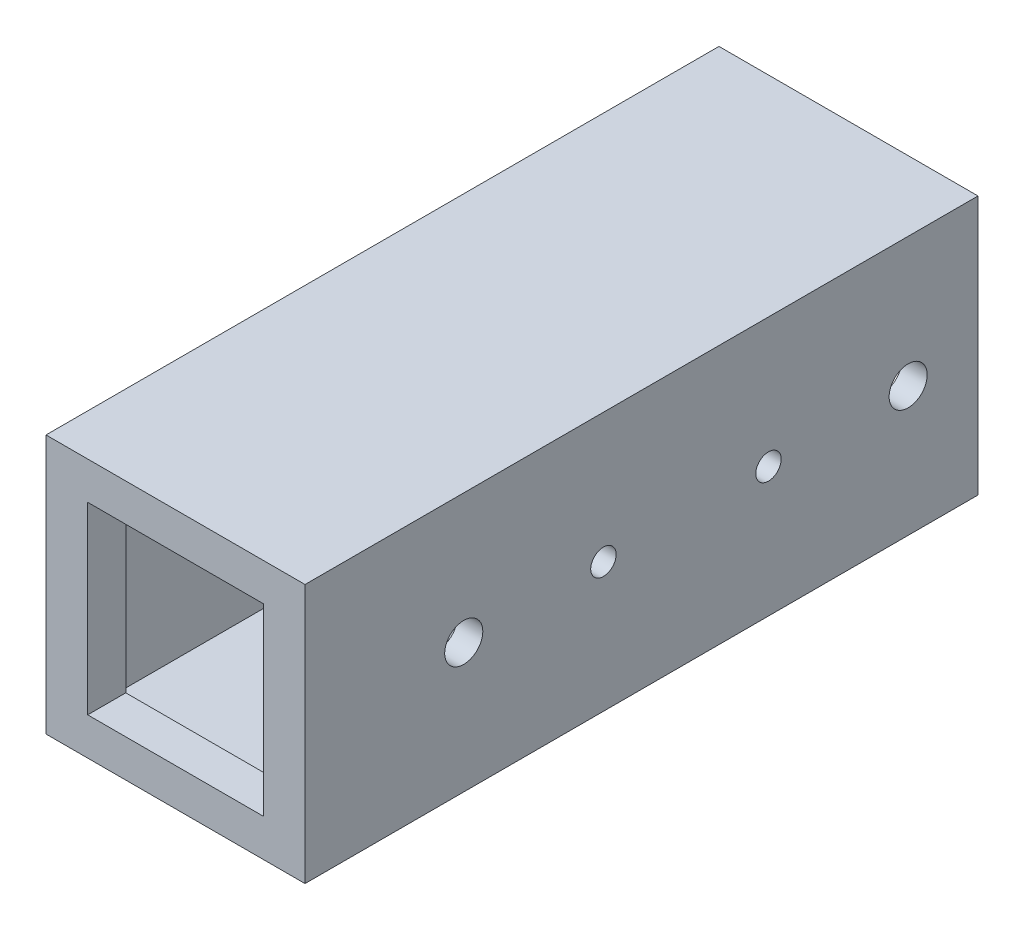
SolidWorks part; units mm, degrees
ref_plane "Front Plane" through (0, 0, 0) normal (0, 0, 1) x (1, 0, 0)
ref_plane "Top Plane" through (0, 0, 0) normal (0, 1, 0) x (1, 0, 0)
ref_plane "Right Plane" through (0, 0, 0) normal (1, 0, 0) x (0, 0, -1)
ref_axis "Axis1" through (0, 0, 0.5) along (0, 0, -1)
sketch "Sketch1" plane through (0, 0, 0) normal (0, 0, 1) x (1, 0, 0)
  line L5 (-10.2, -10.2) -> (10.2, -10.2)
  line L14 (-10.2, -10.2) -> (-10.2, 10.2)
  line L15 (-10.2, 10.2) -> (10.2, 10.2)
  line L16 (10.2, -10.2) -> (10.2, 10.2)
  line L17 (-10.2, -10.2) -> (10.2, 10.2) construction
  line L18 (-10.2, 10.2) -> (10.2, -10.2) construction
  line L19 (-8.2, -8.2) -> (8.2, -8.2)
  line L20 (-8.2, -8.2) -> (-8.2, 8.2)
  line L21 (-8.2, 8.2) -> (8.2, 8.2)
  line L22 (8.2, -8.2) -> (8.2, 8.2)
  line L23 (-8.2, -8.2) -> (8.2, 8.2) construction
  line L24 (-8.2, 8.2) -> (8.2, -8.2) construction
  point P0 (0, 0)
  point P6 (0, 0)
  dimension "D1" = 16.4
  dimension "D2" = 2
extrude "Boss-Extrude1" add sketch "Sketch1" against normal blind 50
sketch "Sketch2" plane through (0, 0, 0) normal (0, 0, 1) x (1, 0, 0)
  line L1 (10.2, 10.2) -> (-10.2, 10.2)
  line L2 (10.2, 10.2) -> (10.2, -10.2)
  line L3 (10.2, -10.2) -> (-10.2, -10.2)
  line L4 (-10.2, 10.2) -> (-10.2, -10.2)
  line L9 (6.9174, -7.2486) -> (-6.9174, -7.2486)
  line L10 (6.9174, -7.2486) -> (6.9174, 7.2486)
  line L11 (6.9174, 7.2486) -> (-6.9174, 7.2486)
  line L12 (-6.9174, -7.2486) -> (-6.9174, 7.2486)
  line L13 (6.9174, -7.2486) -> (-6.9174, 7.2486) construction
  line L14 (6.9174, 7.2486) -> (-6.9174, -7.2486) construction
  point P4 (0, 0)
  point P5 (0, 0)
extrude "Boss-Extrude2" add sketch "Sketch2" along normal blind 3
sketch "Sketch3" plane through (10.2, 0, 0) normal (1, 0, 0) x (0, 0, -1)
  circle A1 centre (44.5, 0) radius 2.1 construction
  circle A4 centre (20.5, 0) radius 1
  circle A5 centre (33.5, 0) radius 3 construction
  circle A6 centre (9.5, 0) radius 1.5
  circle A7 centre (20.5, 0) radius 2.4 construction
  circle A8 centre (9.5, 0) radius 2.1 construction
  circle A9 centre (44.5, 0) radius 2.1 construction
  circle A10 centre (33.5, 0) radius 3 construction
  circle A11 centre (20.5, 0) radius 2.4 construction
  circle A12 centre (9.5, 0) radius 2.1 construction
  circle A13 centre (33.5, 0) radius 1
  circle A14 centre (44.5, 0) radius 1.5
  dimension "D1" = 2
  dimension "D2" = 3
extrude "Cut-Extrude1" cut sketch "Sketch3" against normal through all
fillet "Fillet1" radius 1 4 edges at (-8.2, 0, -50) (0, -8.2, -50) (8.2, 0, -50) (0, 8.2, -50)
